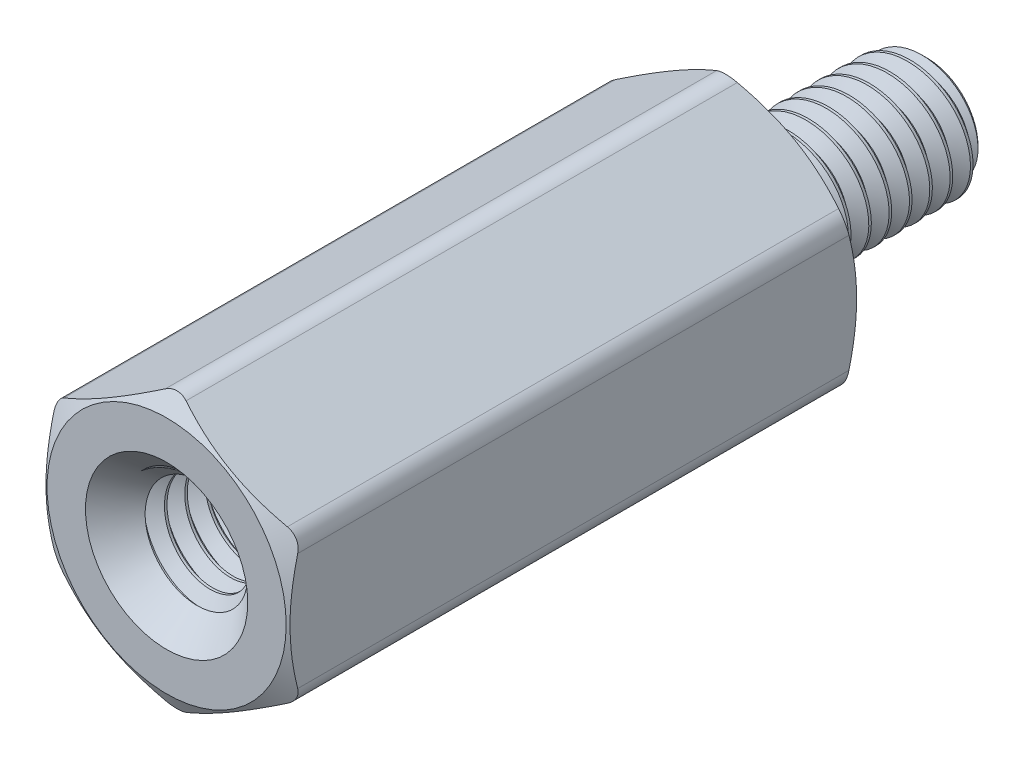
SolidWorks part; units mm, degrees
ref_plane "Front Plane" through (0, 0, 0) normal (0, 0, 1) x (1, 0, 0)
ref_plane "Top Plane" through (0, 0, 0) normal (0, 1, 0) x (1, 0, 0)
ref_plane "Right Plane" through (0, 0, 0) normal (1, 0, 0) x (0, 0, -1)
sketch "Sketch1" plane through (0, 0, 0) normal (0, 0, 1) x (1, 0, 0)
  line L1 (3, 1.7321) -> (0, 3.4641)
  line L2 (0, 3.4641) -> (-3, 1.7321)
  line L3 (-3, 1.7321) -> (-3, -1.7321)
  line L4 (-3, -1.7321) -> (0, -3.4641)
  line L5 (0, -3.4641) -> (3, -1.7321)
  line L6 (3, -1.7321) -> (3, 1.7321)
  circle A0 centre (0, 0) radius 3 construction
  point P10 (0, -3)
  dimension "Hex Size" = 6
sketch "Sketch2" plane through (0, 0, 0) normal (1, 0, 0) x (0, 0, -1)
  line L0 (4.7, 0) -> (-14, 0) construction
  line L2 (0, 1.5) -> (0, -1.5) construction
  line L3 (-7.6, 1.5) -> (-7.6, -1.5) construction
  line L4 (-14.4687, 1.5541) -> (-14.2188, 1.1211) construction
  line L5 (-14.2188, 1.1211) -> (-13.9687, 1.5541) construction
  line L6 (-13.9687, 1.5541) -> (-14.4687, 1.5541) construction
  line L7 (-14.4375, 1.5) -> (-14, 1.5) construction
  line L8 (-14.25, 1.1752) -> (-14.1875, 1.1752) construction
  line L9 (-14.2187, 1.1752) -> (-14.2188, 1.1211) construction
  line L10 (-14.2187, 1.5) -> (-14.2187, 1.5541) construction
  line L11 (4.6688, 1.5541) -> (5.1688, 1.5541) construction
  line L12 (5.1688, 1.5541) -> (4.9188, 1.1211) construction
  line L13 (4.9188, 1.1211) -> (4.6688, 1.5541) construction
  line L14 (4.7, 1.5) -> (5.1375, 1.5) construction
  line L15 (4.8875, 1.1752) -> (4.95, 1.1752) construction
  line L16 (4.9188, 1.1752) -> (4.9188, 1.1211) construction
  line L17 (4.9188, 1.5) -> (4.9188, 1.5541) construction
  line L18 (0, 3.4641) -> (-14, 3.4641) construction
  point P6 (0, 0)
  point P9 (-7.6, 0)
  dimension "Length" = 14
sketch "Sketch3" plane through (0, 0, 0) normal (1, 0, 0) x (0, 0, -1)
  line L0 (-7.6, 0) -> (4.7, 0)
  line L1 (-7.6, 1.5) -> (-7.6, -1.5) construction
  line L2 (4.7, 0) -> (4.7, 1.25)
  line L3 (4.7, 1.25) -> (4.45, 1.5)
  line L4 (4.45, 1.5) -> (0.7515, 1.5)
  line L5 (0.7515, 1.5) -> (0.564, 1.1752)
  line L6 (-7.6, 0) -> (-7.6, 1.25)
  line L7 (-7.6, 1.25) -> (-7.85, 1.5)
  line L8 (-7.85, 1.5) -> (-13.75, 1.5)
  line L9 (-13.75, 1.5) -> (-14, 1.75)
  line L10 (4.45, 0) -> (4.45, -1.5) construction
  line L11 (-14, 1.75) -> (-14, 3)
  line L12 (-14, 3) -> (0, 3)
  line L14 (0.564, 1.1752) -> (0.25, 1.1752)
  line L15 (0, 1.4252) -> (0, 3)
  arc A0 (0, 1.4252) -> (0.25, 1.1752) centre (0.25, 1.4252) ccw
  point P5 (-14, -3)
  point P8 (-12.75, -1.5)
  point P9 (3.45, -1.5)
  point P27 (0, 1.1752)
  dimension "D4" = 0.25
  dimension "D2" = 0.25
  dimension "D1" = 45
  dimension "D6" = 1.25
  dimension "D7" = 60
  dimension "D3" = 1.25
  dimension "D5" = 0.564
revolve "Revolve1" add sketch "Sketch3" angle 360 about L0 region at (0, 1.5494, 4.4309)
sketch "Sketch4" plane through (0, 0, 14) normal (0, 0, 1) x (1, 0, 0)
  line L0 (0, 3) -> (0, 1.5) construction
  line L1 (-3, 1.7321) -> (-3, -1.7321)
  line L2 (-3, -1.7321) -> (0, -3.4641)
  line L3 (0, -3.4641) -> (3, -1.7321)
  line L4 (3, -1.7321) -> (3, 1.7321)
  line L5 (3, 1.7321) -> (0, 3.4641)
  line L6 (0, 3.4641) -> (-3, 1.7321)
  circle A0 centre (0, 0) radius 3 construction
  circle A1 centre (0, 0) radius 2.25
  circle A2 centre (0, 0) radius 3 construction
  point P16 (0, 2.25)
extrude "Boss-Extrude1" add sketch "Sketch4" against normal up to surface (14 mm away) up to face at (0, 3, 0)
sketch "Sketch5" plane through (0, 0, 14) normal (0, 0, 1) x (1, 0, 0)
  line L0 (-0.8604, 1.2287) -> (0.8604, -1.2287) construction
  line L1 (0, 1.5) -> (0, -1.5) construction
  line L3 (0, -2.7928) -> (0, 2.7928) construction
  circle A0 centre (0, 0) radius 2.94
  point P11 (0.8604, -1.2287)
  dimension "D1" = 5.88
  dimension "D2" = 35
extrude "Cut-Extrude1" cut sketch "Sketch5" against normal through all draft 60 flip side to cut
sketch "Sketch6" plane through (0, 0, 0) normal (0, 0, -1) x (-1, 0, 0)
  circle A0 centre (0, 0) radius 2.94
  circle A1 centre (0, 0) radius 2.94 construction
extrude "Cut-Extrude2" cut sketch "Sketch6" against normal through all draft 60 flip side to cut
fillet "Fillet1" radius 0.51 6 edges at (0, 3.4641, 7) (-3, -1.7321, 7) (0, -3.4641, 7) (3, -1.7321, 7) (3, 1.7321, 7) (-3, 1.7321, 7)
sketch "Drawing1" plane through (0, 0, 0) normal (1, 0, 0) x (0, 0, -1)
  line L0 (-14, 1.5) -> (-7.6, 1.5) construction
  line L1 (-7.6, 1.5) -> (-7.6, -1.5) construction
  line L2 (-7.6, -1.5) -> (-14, -1.5) construction
sketch "Sketch7" plane through (0, 0, 0) normal (-1, 0, 0) x (0, 0, 1)
  line L0 (-4.8875, 1.1752) -> (-4.95, 1.1752)
  line L1 (-4.95, 1.1752) -> (-5.1531, 1.5271)
  line L2 (-5.1688, 1.5541) -> (-4.9188, 1.1211) construction
  line L3 (-5.1531, 1.5271) -> (-4.6844, 1.5271)
  line L4 (-4.9188, 1.1211) -> (-4.6688, 1.5541) construction
  line L5 (-4.6844, 1.5271) -> (-4.8875, 1.1752)
  line L6 (-4.9188, 1.5) -> (-4.9188, 1.5541) construction
  point P12 (-4.9188, 1.5271)
sketch "Sketch8" plane through (0, 0, -4.7) normal (0, 0, -1) x (-1, 0, 0)
  circle A0 centre (0, 0) radius 1.5
curve "Helix/Spiral1" pitch 0.5 height 4.559 radius 1.5 centre (0, 0, -4.7) axis (0, 0, 1) start towards (0, 1, 0)
sweep "Cut-Sweep1" cut profiles "Sketch7" path "Helix/Spiral1" align with end faces yes
sketch "Sketch9" plane through (0, 0, 7.6) normal (0, 0, 1) x (1, 0, 0)
  circle A0 centre (0, 0) radius 1.75
extrude "Boss-Extrude2" add sketch "Sketch9" along normal up to surface (6.4 mm away) up to face at (0, 1.75, 14)
sketch "Sketch10" plane through (0, 0, 0) normal (1, 0, 0) x (0, 0, -1)
  line L0 (4.7, 0) -> (-14, 0) construction
  line L1 (-7.6, 1.5) -> (-14, 1.5)
  line L2 (-7.6, 1.5) -> (-7.6, 0)
  line L3 (-7.6, 0) -> (-14, 0)
  line L4 (-14, 1.5) -> (-14, 0)
revolve "Revolve2" add sketch "Sketch10" angle 360 about L0
sketch "Sketch11" plane through (0, 0, 14) normal (0, 0, 1) x (1, 0, 0)
  circle A0 centre (0, 0) radius 1.5
  circle A1 centre (0, 0) radius 1.5 construction
sketch "Sketch12" plane through (0, 0, 0) normal (1, 0, 0) x (0, 0, -1)
  line L0 (-14.25, 1.1752) -> (-14.1875, 1.1752)
  line L1 (-14.1875, 1.1752) -> (-13.9844, 1.5271)
  line L2 (-14.2188, 1.1211) -> (-13.9687, 1.5541) construction
  line L3 (-13.9844, 1.5271) -> (-14.4531, 1.5271)
  line L4 (-14.4687, 1.5541) -> (-14.2187, 1.1211) construction
  line L5 (-14.4531, 1.5271) -> (-14.25, 1.1752)
  line L6 (-14.2187, 1.5) -> (-14.2187, 1.5541) construction
  point P12 (-14.2187, 1.5271)
curve "Helix/Spiral2" pitch 0.5 height 6.9 radius 1.5 centre (0, 0, 14) axis (0, 0, -1) start towards (0, 1, 0)
sweep "Cut-Sweep2" cut profiles "Sketch12" path "Helix/Spiral2" align with end faces yes
combine bodies "Combine1" operation type subtract main body 113 bodies to subtract 114
sketch "Sketch13" plane through (0, 0, 14) normal (0, 0, 1) x (1, 0, 0)
  circle A0 centre (0, 0) radius 1.995
  dimension "D1" = 3.99
extrude "Cut-Extrude3" cut sketch "Sketch13" against normal through all draft 45
equation "\"Thread Pitch (B)/8@Sketch2\" = \"Thread Pitch (B)@Sketch2\" / 8"
equation "\"Thread Pitch (A)/8@Sketch2\" = \"Thread Pitch (A)@Sketch2\" / 8"
equation "\"D1@Sketch5\"=\"Hex Size@Sketch1\" * .98"
equation "\"D1@Fillet1\"=\"Hex Size@Sketch1\" * .085"
equation "\"D2@Sketch3\"=\"Thread Pitch (A)@Sketch2\" * .5"
equation "\"D4@Sketch3\" = \"D2@Sketch3\""
equation "\"D6@Sketch3\" = \"Thread Pitch (A)@Sketch2\" * 2.5"
equation "\"D3@Helix/Spiral1\" = \"Thread Length (A)@Sketch2\" - \"D5@Sketch3\" * .25"
equation "\"D4@Helix/Spiral1\" = \"Thread Pitch (A)@Sketch2\""
equation "\"D3@Sketch3\" = \"Thread Pitch (B)@Sketch2\" * 2.5"
equation "\"D5@Sketch3\" = \"Thread Length (A)@Sketch2\" * .12"
equation "\"D3@Helix/Spiral2\" = \"Minimum Thread Length (B)@Sketch2\" + \"Thread Pitch (B)@Sketch2\""
equation "\"D4@Helix/Spiral2\" = \"Thread Pitch (B)@Sketch2\""
equation "\"D1@Sketch13\"=(\"Hex Size@Sketch1\"-\"Thread Size (A)@Sketch2\")*.33+\"Thread Size (A)@Sketch2\""
